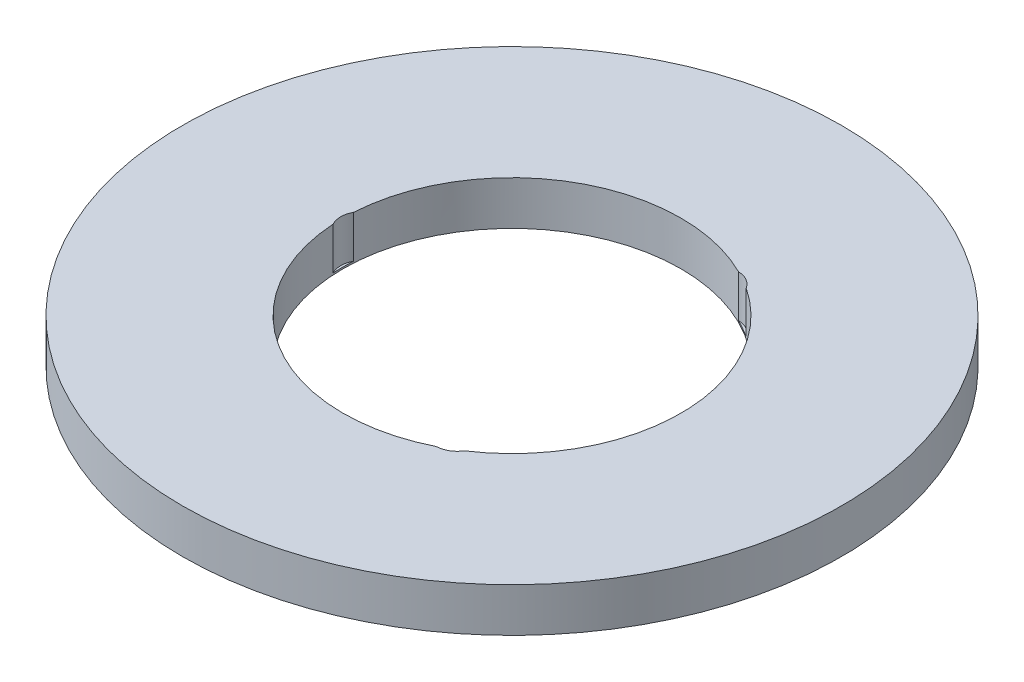
SolidWorks part; units mm, degrees
ref_plane "Front Plane" through (0, 0, 0) normal (0, 0, 1) x (1, 0, 0)
ref_plane "Top Plane" through (0, 0, 0) normal (0, 1, 0) x (1, 0, 0)
ref_plane "Right Plane" through (0, 0, 0) normal (1, 0, 0) x (0, 0, -1)
sketch "Sketch1" plane through (0, 0, 0) normal (0, 1, 0) x (1, 0, 0)
  circle A0 centre (0, 0) radius 97.5
  dimension "FLANGE_OD" = 195
extrude "Boss-Extrude1" add sketch "Sketch1" along normal blind 13
sketch "Sketch2" plane through (0, 0, 0) normal (0, 1, 0) x (1, 0, 0)
  circle A0 centre (0, 0) radius 50
  dimension "BORE_D" = 100
extrude "Cut-Extrude1" cut sketch "Sketch2" along normal through all
sketch "Sketch3" plane through (0, 13, 0) normal (0, 1, 0) x (1, 0, 0)
  circle A0 centre (0, 0) radius 44.2372 construction
  circle A1 centre (-44.2372, 0) radius 6.4342
  dimension "BOLT_D" = 12.8683
  dimension "BOLT_PCD" = 88.4744
extrude "Cut-Extrude2" cut sketch "Sketch3" against normal blind 12.528
pattern_circular "CirPattern1" count 3 over 360 about axis through (0, 0, 0) along (0, 1, 0) of "Cut-Extrude2"
